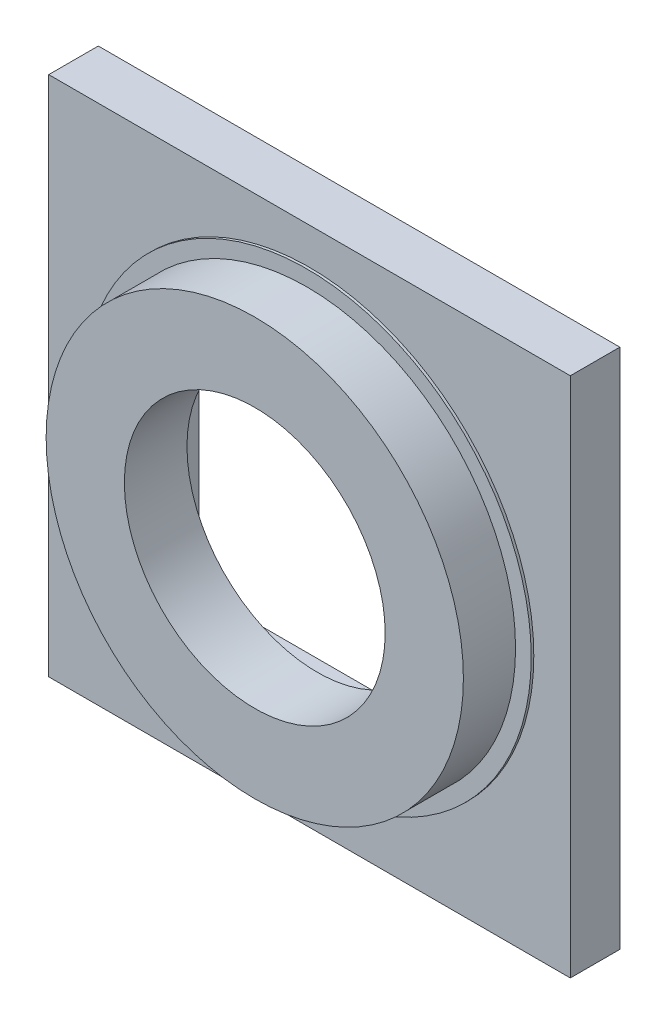
SolidWorks part; units mm, degrees
ref_plane "Plan de face" through (0, 0, 0) normal (0, 0, 1) x (1, 0, 0)
ref_plane "Plan de dessus" through (0, 0, 0) normal (0, 1, 0) x (1, 0, 0)
ref_plane "Plan de droite" through (0, 0, 0) normal (1, 0, 0) x (0, 0, -1)
sketch "Esquisse1" plane through (0, 0, 0) normal (0, 0, 1) x (1, 0, 0)
  line L1 (28, 28) -> (-28, 28)
  line L2 (28, 28) -> (28, -28)
  line L3 (28, -28) -> (-28, -28)
  line L4 (-28, 28) -> (-28, -28)
  line L5 (28, 28) -> (-28, -28) construction
  line L6 (28, -28) -> (-28, 28) construction
  line L7 (50, 50) -> (-50, 50)
  line L8 (50, 50) -> (50, -50)
  line L9 (50, -50) -> (-50, -50)
  line L10 (-50, 50) -> (-50, -50)
  line L11 (50, 50) -> (-50, -50) construction
  line L12 (50, -50) -> (-50, 50) construction
  circle A0 centre (0, 0) radius 40 construction
  point P0 (0, 0)
  dimension "D2" = 80
  dimension "D1" = 56
  dimension "D3" = 100
extrude "Boss.-Extru.1" add sketch "Esquisse1" along normal blind 10
fillet "Congé1" radius 3.5 4 edges at (-28, -28, 5) (28, 28, 5) (-28, 28, 5) (28, -28, 5)
sketch "Esquisse3" plane through (0, 0, 10) normal (0, 0, 1) x (1, 0, 0)
  line L5 (-28, 24.5) -> (-28, -24.5)
  line L6 (24.5, 28) -> (-24.5, 28)
  line L7 (28, -24.5) -> (28, 24.5)
  line L8 (-24.5, -28) -> (24.5, -28)
  line L9 (-28, 24.5) -> (-28, -24.5)
  line L10 (24.5, 28) -> (-24.5, 28)
  line L11 (28, -24.5) -> (28, 24.5)
  line L12 (-24.5, -28) -> (24.5, -28)
  circle A0 centre (0, 0) radius 40
  arc A5 (-24.5, 28) -> (-28, 24.5) centre (-24.5, 24.5) ccw
  arc A6 (28, 24.5) -> (24.5, 28) centre (24.5, 24.5) ccw
  arc A7 (24.5, -28) -> (28, -24.5) centre (24.5, -24.5) ccw
  arc A8 (-28, -24.5) -> (-24.5, -28) centre (-24.5, -24.5) ccw
  arc A9 (-24.5, 28) -> (-28, 24.5) centre (-24.5, 24.5) ccw
  arc A10 (28, 24.5) -> (24.5, 28) centre (24.5, 24.5) ccw
  arc A11 (24.5, -28) -> (28, -24.5) centre (24.5, -24.5) ccw
  arc A12 (-28, -24.5) -> (-24.5, -28) centre (-24.5, -24.5) ccw
  dimension "D1" = 80
  dimension "D2" = 0
extrude "Boss.-Extru.2" add sketch "Esquisse3" along normal blind 10
sketch "Esquisse4" plane through (0, 0, 10) normal (0, 0, 1) x (1, 0, 0)
  circle A0 centre (0, 0) radius 43
  circle A1 centre (0, 0) radius 40 construction
  dimension "D1" = 3
extrude "Enlèv. mat.-Extru.2" cut sketch "Esquisse4" against normal blind 0.5 flip side to cut
sketch "Esquisse5" plane through (0, 0, 0) normal (0, 0, -1) x (-1, 0, 0)
  line L1 (30.7, -30.7) -> (-30.7, -30.7)
  line L2 (30.7, -30.7) -> (30.7, 30.7)
  line L3 (30.7, 30.7) -> (-30.7, 30.7)
  line L4 (-30.7, -30.7) -> (-30.7, 30.7)
  line L5 (30.7, -30.7) -> (-30.7, 30.7) construction
  line L6 (30.7, 30.7) -> (-30.7, -30.7) construction
  point P0 (0, 0)
  dimension "D1" = 61.4
extrude "Enlèv. mat.-Extru.3" cut sketch "Esquisse5" against normal blind 9
sketch "Esquisse6" plane through (0, 0, 9) normal (0, 0, -1) x (-1, 0, 0)
  line L4 (-30.7, 30.7) -> (-30.7, -30.7)
  line L5 (-30.7, -30.7) -> (30.7, -30.7)
  line L6 (30.7, -30.7) -> (30.7, 30.7)
  line L7 (30.7, 30.7) -> (-30.7, 30.7)
  line L8 (-30.7, 30.7) -> (-30.7, -30.7)
  line L9 (-30.7, -30.7) -> (30.7, -30.7)
  line L10 (30.7, -30.7) -> (30.7, 30.7)
  line L11 (30.7, 30.7) -> (-30.7, 30.7)
  line L13 (28, -24.5) -> (28, 24.5)
  line L14 (-24.5, -28) -> (24.5, -28)
  line L15 (-28, 24.5) -> (-28, -24.5)
  line L16 (24.5, 28) -> (-24.5, 28)
  line L17 (28, -24.5) -> (28, 24.5)
  line L18 (-24.5, -28) -> (24.5, -28)
  line L19 (-28, 24.5) -> (-28, -24.5)
  line L20 (24.5, 28) -> (-24.5, 28)
  arc A4 (28, 24.5) -> (24.5, 28) centre (24.5, 24.5) ccw
  arc A5 (24.5, -28) -> (28, -24.5) centre (24.5, -24.5) ccw
  arc A6 (-28, -24.5) -> (-24.5, -28) centre (-24.5, -24.5) ccw
  arc A7 (-24.5, 28) -> (-28, 24.5) centre (-24.5, 24.5) ccw
  arc A8 (28, 24.5) -> (24.5, 28) centre (24.5, 24.5) ccw
  arc A9 (24.5, -28) -> (28, -24.5) centre (24.5, -24.5) ccw
  arc A10 (-28, -24.5) -> (-24.5, -28) centre (-24.5, -24.5) ccw
  arc A11 (-24.5, 28) -> (-28, 24.5) centre (-24.5, 24.5) ccw
  dimension "D1" = 0
  dimension "D2" = 0
extrude "Boss.-Extru.3" add sketch "Esquisse6" along normal blind 1
sketch "Esquisse7" plane through (0, 0, 8) normal (0, 0, -1) x (-1, 0, 0)
  line L5 (-24.5, -28) -> (24.5, -28)
  line L6 (28, -24.5) -> (28, 24.5)
  line L7 (24.5, 28) -> (-24.5, 28)
  line L8 (-28, 24.5) -> (-28, -24.5)
  line L9 (-24.5, -28) -> (24.5, -28)
  line L10 (28, -24.5) -> (28, 24.5)
  line L11 (24.5, 28) -> (-24.5, 28)
  line L12 (-28, 24.5) -> (-28, -24.5)
  circle A0 centre (0, 0) radius 25
  arc A5 (24.5, -28) -> (28, -24.5) centre (24.5, -24.5) ccw
  arc A6 (28, 24.5) -> (24.5, 28) centre (24.5, 24.5) ccw
  arc A7 (-24.5, 28) -> (-28, 24.5) centre (-24.5, 24.5) ccw
  arc A8 (-28, -24.5) -> (-24.5, -28) centre (-24.5, -24.5) ccw
  arc A9 (24.5, -28) -> (28, -24.5) centre (24.5, -24.5) ccw
  arc A10 (28, 24.5) -> (24.5, 28) centre (24.5, 24.5) ccw
  arc A11 (-24.5, 28) -> (-28, 24.5) centre (-24.5, 24.5) ccw
  arc A12 (-28, -24.5) -> (-24.5, -28) centre (-24.5, -24.5) ccw
  dimension "D1" = 50
  dimension "D2" = 0
extrude "Boss.-Extru.4" add sketch "Esquisse7" against normal up to surface (12 mm away) up to face at (40, 0, 20)
